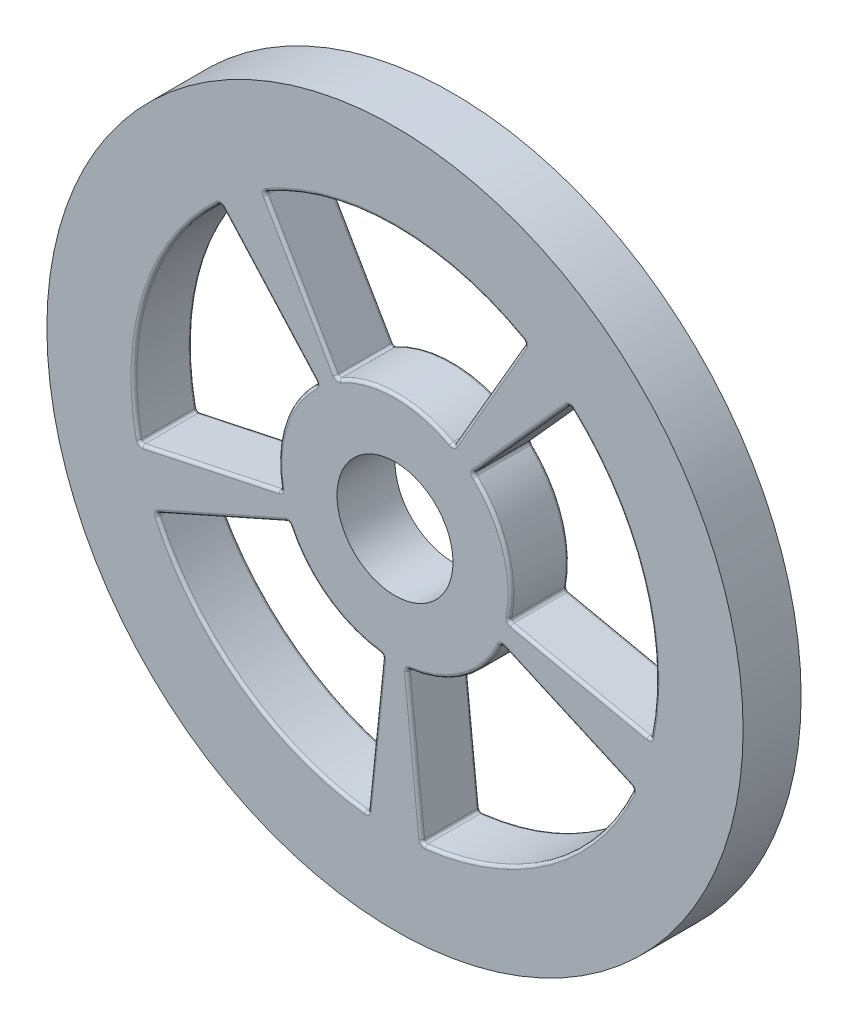
SolidWorks part; units mm, degrees
material "6061-T6 (SS)"
ref_plane "Front Plane" through (0, 0, 0) normal (0, 0, 1) x (1, 0, 0)
ref_plane "Top Plane" through (0, 0, 0) normal (0, 1, 0) x (1, 0, 0)
ref_plane "Right Plane" through (0, 0, 0) normal (1, 0, 0) x (0, 0, -1)
sketch "Sketch1" plane through (0, 0, 0) normal (0, 0, 1) x (1, 0, 0)
  circle A0 centre (0, 0) radius 60
  circle A1 centre (0, 0) radius 10
  dimension "D1" = 120
  dimension "D2" = 20
extrude "Boss-Extrude1" add sketch "Sketch1" along normal mid plane 10
sketch "Sketch2" plane through (0, 0, 5) normal (0, 0, 1) x (1, 0, 0)
  line L0 (-22.5339, 38.9515) -> (-10.0151, 17.3118)
  line L1 (10.0151, 17.3118) -> (22.5339, 38.9515)
  line L2 (30.0817, 33.4677) -> (13.3697, 14.8745)
  line L3 (19.5593, -4.1753) -> (44.0085, -9.3944)
  line L4 (41.1255, -18.2673) -> (18.278, -8.1188)
  line L5 (2.0732, -19.8923) -> (4.6648, -44.7576)
  line L6 (-4.6648, -44.7576) -> (-2.0732, -19.8923)
  line L7 (-18.278, -8.1188) -> (-41.1255, -18.2673)
  line L8 (-44.0085, -9.3944) -> (-19.5593, -4.1753)
  line L9 (-13.3697, 14.8745) -> (-30.0817, 33.4677)
  arc A0 (10.0151, 17.3118) -> (-10.0151, 17.3118) centre (0, 0) ccw
  arc A1 (22.5339, 38.9515) -> (-22.5339, 38.9515) centre (0, 0) ccw
  arc A2 (44.0085, -9.3944) -> (30.0817, 33.4677) centre (0, 0) ccw
  arc A3 (19.5593, -4.1753) -> (13.3697, 14.8745) centre (0, 0) ccw
  arc A4 (4.6648, -44.7576) -> (41.1255, -18.2673) centre (0, 0) ccw
  arc A5 (2.0732, -19.8923) -> (18.278, -8.1188) centre (0, 0) ccw
  arc A6 (-41.1255, -18.2673) -> (-4.6648, -44.7576) centre (0, 0) ccw
  arc A7 (-18.278, -8.1188) -> (-2.0732, -19.8923) centre (0, 0) ccw
  arc A8 (-30.0817, 33.4677) -> (-44.0085, -9.3944) centre (0, 0) ccw
  arc A9 (-13.3697, 14.8745) -> (-19.5593, -4.1753) centre (0, 0) ccw
  point P24 (0, 0)
  dimension "D1" = 90
  dimension "D2" = 40
  dimension "D3" = 5
extrude "Cut-Extrude1" cut sketch "Sketch2" against normal through all
fillet "Fillet2" radius 0.5 60 edges at (3.369, -32.3249, -5) (3.369, -32.3249, 5) (29.7017, -13.1931, -5) (29.7017, -13.1931, 5) (-29.7017, -13.1931, -5) (-29.7017, -13.1931, 5) (-3.369, -32.3249, -5) (-3.369, -32.3249, 5) (-21.7257, 24.1711, -5) (-21.7257, 24.1711, 5) (-31.7839, -6.7848, -5) (-31.7839, -6.7848, 5) (16.2745, 28.1317, -5) (16.2745, 28.1317, 5) (-16.2745, 28.1317, -5) (-16.2745, 28.1317, 5) (31.7839, -6.7848, -5) (31.7839, -6.7848, 5) (21.7257, 24.1711, -5) (21.7257, 24.1711, 5) (-2.0732, -19.8923, 0) (-11.7557, -16.1803, -5) (-18.278, -8.1188, 0) (-11.7557, -16.1803, 5) (-19.5593, -4.1753, 0) (-19.0211, 6.1803, -5) (-13.3697, 14.8745, 0) (-19.0211, 6.1803, 5) (-10.0151, 17.3118, 0) (0, 20, -5) (10.0151, 17.3118, 0) (0, 20, 5) (13.3697, 14.8745, 0) (19.0211, 6.1803, -5) (19.5593, -4.1753, 0) (19.0211, 6.1803, 5) (18.278, -8.1188, 0) (11.7557, -16.1803, -5) (2.0732, -19.8923, 0) (11.7557, -16.1803, 5) (4.6648, -44.7576, 0) (26.4503, -36.4058, -5) (41.1255, -18.2673, 0) (26.4503, -36.4058, 5) (-41.1255, -18.2673, 0) (-26.4503, -36.4058, -5) (-4.6648, -44.7576, 0) (-26.4503, -36.4058, 5) (-30.0817, 33.4677, 0) (-42.7975, 13.9058, -5) (-44.0085, -9.3944, 0) (-42.7975, 13.9058, 5) (22.5339, 38.9515, 0) (0, 45, -5) (-22.5339, 38.9515, 0) (0, 45, 5) (44.0085, -9.3944, 0) (42.7975, 13.9058, -5) (30.0817, 33.4677, 0) (42.7975, 13.9058, 5)
ref_axis "Axis1" through (0, 0, 5) along (0, 0, -1)
